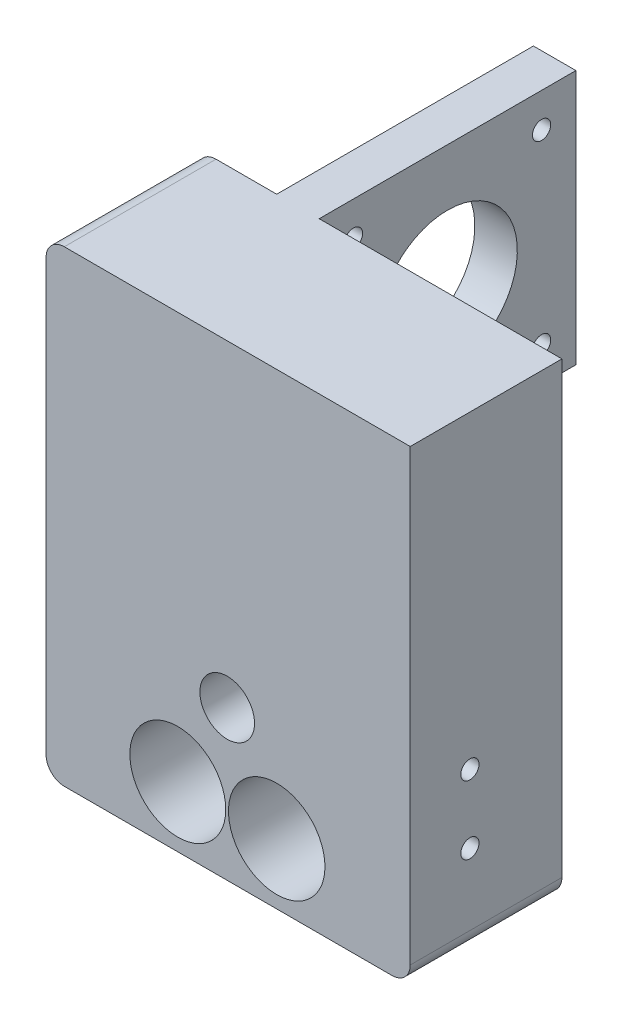
SolidWorks part; units mm, degrees
ref_plane "Plan de face" through (0, 0, 0) normal (0, 0, 1) x (1, 0, 0)
ref_plane "Plan de dessus" through (0, 0, 0) normal (0, 1, 0) x (1, 0, 0)
ref_plane "Plan de droite" through (0, 0, 0) normal (1, 0, 0) x (0, 0, -1)
sketch "Esquisse1" plane through (0, 0, 0) normal (0, 0, 1) x (1, 0, 0)
  line L1 (0, 0) -> (100, 0)
  line L2 (0, 0) -> (0, 100)
  line L3 (0, 100) -> (100, 100)
  line L4 (100, 0) -> (100, 100)
  dimension "D1" = 100
  dimension "D2" = 100
extrude "Boss.-Extru.1" add sketch "Esquisse1" along normal blind 25
sketch "Esquisse2" plane through (0, 0, 0) normal (0, 0, 1) x (1, 0, 0)
  line L1 (100, 0) -> (100, 100) construction
  line L2 (0, 0) -> (100, 0) construction
  circle A0 centre (61.7, 9.9946) radius 7.9
  circle A1 centre (78, 10) radius 7.95
  circle A2 centre (69.8451, 24.6423) radius 4.5
  dimension "D1" = 9
  dimension "D2" = 15.9
  dimension "D3" = 15.8
  dimension "D7" = 10
  dimension "D4" = 16.3
  dimension "D5" = 16.76
  dimension "D6" = 16.76
  dimension "D8" = 22
extrude "Enlèv. mat.-Extru.1" cut sketch "Esquisse2" along normal through all
sketch "Esquisse3" plane through (0, 0, 0) normal (0, 1, 0) x (1, 0, 0)
  line L1 (100, -25) -> (100, 0) construction
  line L2 (0, 0) -> (100, 0) construction
  circle A0 centre (48, -12.5) radius 4.3
  circle A1 centre (92, -12.5) radius 4.3
  dimension "D1" = 8.6
  dimension "D2" = 8.6
  dimension "D4" = 8
  dimension "D6" = 12.5
  dimension "D3" = 44
  dimension "D5" = 12.5
extrude "Enlèv. mat.-Extru.3" cut sketch "Esquisse3" along normal blind 10
sketch "Esquisse4" plane through (0, 0, 0) normal (0, 0, 1) x (1, 0, 0)
  line L0 (100, 0) -> (100, 100) construction
  line L1 (60, 77) -> (53, 77)
  line L2 (60, 77) -> (60, 35)
  line L3 (60, 35) -> (53, 35)
  line L4 (53, 77) -> (53, 35)
  line L5 (0, 0) -> (100, 0) construction
  point P4 (56.5, 77)
  dimension "D1" = 3.5
  dimension "D2" = 42
  dimension "D3" = 40
  dimension "D4" = 35
extrude "Boss.-Extru.2" add sketch "Esquisse4" against normal blind 42.3
sketch "Esquisse5" plane through (60, 0, 0) normal (1, 0, 0) x (0, 0, -1)
  line L0 (0, 0) -> (0, 100) construction
  line L1 (42.3, 35) -> (0, 35) construction
  line L2 (42.3, 77) -> (0, 77) construction
  line L4 (42.3, 35) -> (42.3, 77) construction
  line L5 (0, 0) -> (0, 100) construction
  circle A0 centre (36.65, 71.35) radius 1.5
  circle A1 centre (36.65, 40.65) radius 1.5
  circle A2 centre (5.65, 40.65) radius 1.5
  circle A3 centre (5.65, 71.35) radius 1.5
  dimension "D1" = 3
  dimension "D2" = 3
  dimension "D3" = 3
  dimension "D4" = 3
  dimension "D5" = 5.65
  dimension "D6" = 5.65
  dimension "D7" = 5.65
  dimension "D8" = 5.65
  dimension "D9" = 5.65
  dimension "D10" = 5.65
  dimension "D11" = 5.65
  dimension "D12" = 5.65
extrude "Enlèv. mat.-Extru.4" cut sketch "Esquisse5" against normal blind 12
sketch "Esquisse6" plane through (0, 0, 0) normal (0, 0, 1) x (1, 0, 0)
  line L0 (0, 0) -> (100, 0) construction
  line L1 (40, 0) -> (0, 0)
  line L2 (40, 0) -> (40, 100)
  line L3 (40, 100) -> (0, 100)
  line L4 (0, 0) -> (0, 100)
  dimension "D1" = 40
extrude "Enlèv. mat.-Extru.6" cut sketch "Esquisse6" along normal through all
sketch "Esquisse7" plane through (0, 0, 0) normal (0, 0, 1) x (1, 0, 0)
  line L0 (40, 0) -> (40, 100) construction
  line L1 (100, 100) -> (40, 100)
  line L2 (100, 100) -> (100, 77.3119)
  line L3 (100, 77.3119) -> (40, 77.3119)
  line L4 (40, 100) -> (40, 77.3119)
sketch "Esquisse8" plane through (0, 0, 0) normal (0, 0, -1) x (-1, 0, 0)
  line L1 (-62.691, 21.8527) -> (-63.8522, 29.4431)
  line L2 (-63.8522, 29.4431) -> (-71.0064, 32.2327)
  line L3 (-71.0064, 32.2327) -> (-76.9993, 27.4318)
  line L4 (-76.9993, 27.4318) -> (-75.838, 19.8414)
  line L5 (-75.838, 19.8414) -> (-68.6839, 17.0518)
  line L6 (-68.6839, 17.0518) -> (-62.691, 21.8527)
  circle A0 centre (-69.8451, 24.6423) radius 6.65 construction
  dimension "D1" = 13.3
extrude "Enlèv. mat.-Extru.8" cut sketch "Esquisse8" against normal blind 7.5
sketch "Esquisse9" plane through (0, 0, 0) normal (0, 0, -1) x (-1, 0, 0)
  line L1 (-100, 77) -> (-40, 77)
  line L2 (-100, 77) -> (-100, 100)
  line L3 (-100, 100) -> (-40, 100)
  line L4 (-40, 77) -> (-40, 100)
extrude "Enlèv. mat.-Extru.9" cut sketch "Esquisse9" against normal through all
fillet "Congé2" radius 3 3 edges at (100, 0, 12.5) (40, 77, 12.5) (40, 0, 12.5)
sketch "Esquisse10" plane through (53, 0, 0) normal (-1, 0, 0) x (0, 0, 1)
  line L0 (-42.3, 77) -> (-42.3, 35) construction
  line L1 (-42.3, 35) -> (0, 35) construction
  circle A0 centre (-21.15, 56.15) radius 11.5
  dimension "D1" = 21.15
  dimension "D2" = 21.15
  dimension "D3" = 23
extrude "Enlèv. mat.-Extru.10" cut sketch "Esquisse10" against normal through all
sketch "Esquisse11" plane through (100, 0, 0) normal (1, 0, 0) x (0, 0, -1)
  circle A0 centre (-15.164, 26) radius 1.5
  circle A1 centre (-15.164, 14.7519) radius 1.5
  dimension "D1" = 3
  dimension "D2" = 3
extrude "Enlèv. mat.-Extru.11" cut sketch "Esquisse11" against normal blind 3
